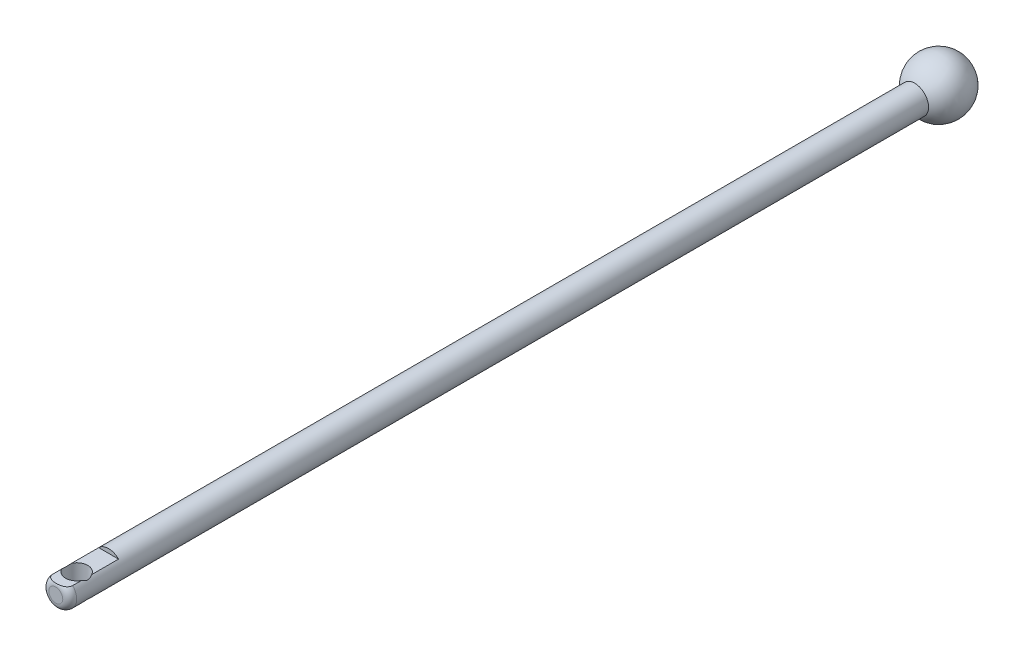
SolidWorks part; units mm, degrees
ref_plane "Front Plane" through (0, 0, 0) normal (0, 0, 1) x (1, 0, 0)
ref_plane "Top Plane" through (0, 0, 0) normal (0, 1, 0) x (1, 0, 0)
ref_plane "Right Plane" through (0, 0, 0) normal (1, 0, 0) x (0, 0, -1)
sketch "Sketch1" plane through (0, 0, 0) normal (0, 0, 1) x (1, 0, 0)
  circle A0 centre (-5.9113, 0) radius 1
extrude "Boss-Extrude1" add sketch "Sketch1" along normal blind 65
sketch "Sketch3" plane through (0, 0, 0) normal (0, 1, 0) x (1, 0, 0)
  line L1 (-6.9113, 0) -> (-6.9113, -65) construction
  line L2 (-6.9113, -65) -> (-4.9113, -65) construction
  circle A1 centre (-5.9113, -63.5) radius 0.8
  dimension "D4" = 1.5
  dimension "D5" = 1.6
  dimension "D6" = 1
extrude "Cut-Extrude1" cut sketch "Sketch3" against normal blind 50 and the other way blind 50
fillet "Fillet1" radius 0.5 2 edges at (-4.9113, 0, 0) (-4.9113, 0, 65)
ref_plane "Plane1" through (0, 0, 0) normal (0, 1, 0) x (1, 0, 0)
sketch "Sketch7" plane through (0, 0, 0) normal (0, 1, 0) x (1, 0, 0)
  line L0 (-5.9113, 1.7126) -> (-5.9113, -4.8726) construction
  line L1 (-5.9113, 0.5) -> (-5.9113, -3.5)
  line L2 (-5.4113, 0) -> (-6.4113, 0) construction
  arc A0 (-5.9113, -3.5) -> (-5.9113, 0.5) centre (-5.9113, -1.5) ccw
  dimension "D1" = 4
  dimension "D2" = 1.5
revolve "Revolve3" add sketch "Sketch7" angle 360 about L0
ref_plane "Plane2" through (0, 1, 0) normal (0, 1, 0) x (1, 0, 0)
sketch "Sketch8" plane through (0, 1, 0) normal (0, 1, 0) x (1, 0, 0)
  line L1 (-7.5234, -61.2022) -> (-4.235, -61.2022)
  line L2 (-7.5234, -61.2022) -> (-7.5234, -65.4972)
  line L3 (-7.5234, -65.4972) -> (-4.235, -65.4972)
  line L4 (-4.235, -61.2022) -> (-4.235, -65.4972)
extrude "Cut-Extrude2" cut sketch "Sketch8" against normal blind 0.3
